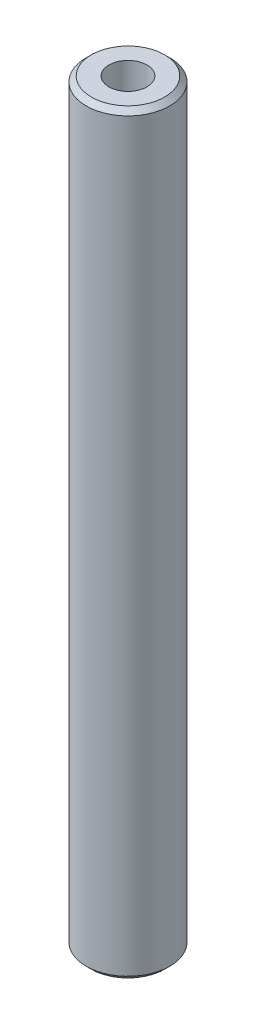
SolidWorks part; units mm, degrees
ref_plane "Front Plane" through (0, 0, 0) normal (0, 0, 1) x (1, 0, 0)
ref_plane "Top Plane" through (0, 0, 0) normal (0, 1, 0) x (1, 0, 0)
ref_plane "Right Plane" through (0, 0, 0) normal (1, 0, 0) x (0, 0, -1)
sketch "Sketch1" plane through (0, 0, 0) normal (0, 1, 0) x (1, 0, 0)
  circle A0 centre (0, 0) radius 5
  dimension "SHAFT_OD" = 10
extrude "Boss-Extrude1" add sketch "Sketch1" along normal blind 90.4106
sketch "Sketch2" plane through (0, 0, 0) normal (0, 1, 0) x (1, 0, 0)
  circle A0 centre (0, 0) radius 2.2778
  dimension "BORE_D" = 4.5556
extrude "Cut-Extrude1" cut sketch "Sketch2" along normal through all
chamfer "Chamfer1" distance 0.614 angle 45 2 edges at (0, 90.4106, 5) (0, 0, 5)
